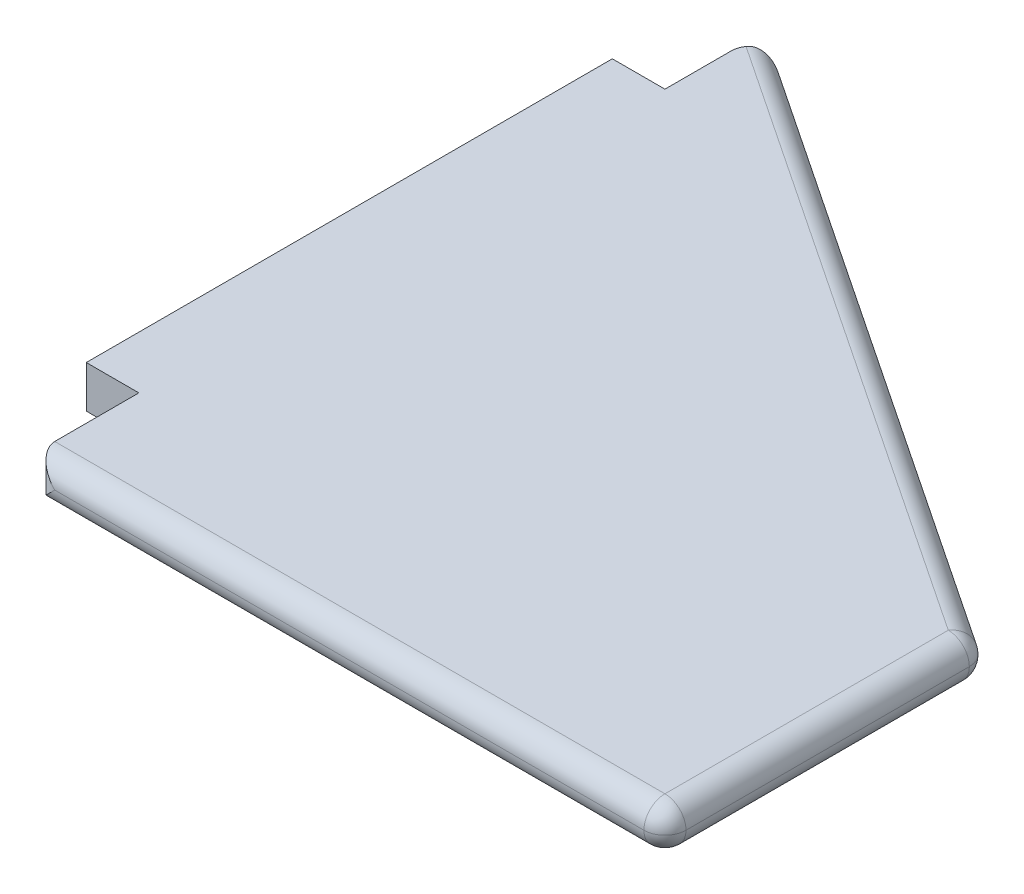
SolidWorks part; units mm, degrees
ref_plane "Front Plane" through (0, 0, 0) normal (0, 0, 1) x (1, 0, 0)
ref_plane "Top Plane" through (0, 0, 0) normal (0, 1, 0) x (1, 0, 0)
ref_plane "Right Plane" through (0, 0, 0) normal (1, 0, 0) x (0, 0, -1)
sketch "Sketch1" plane through (0, 0, 0) normal (0, 1, 0) x (1, 0, 0)
  line L0 (0, 0) -> (0, 31.75)
  line L1 (0, 31.75) -> (3.175, 31.75)
  line L2 (3.175, 31.75) -> (3.175, 38.1)
  line L3 (3.175, 38.1) -> (41.275, 12.7)
  line L4 (41.275, 12.7) -> (41.275, -6.35)
  line L6 (3.175, -6.35) -> (3.175, 0)
  line L7 (3.175, 0) -> (0, 0)
  line L8 (3.175, -6.35) -> (41.275, -6.35)
  point P9 (0, 0)
  point P10 (0, 0)
  dimension "D1" = 38.1
  dimension "D2" = 44.45
  dimension "D3" = 31.75
  dimension "D4" = 19.05
  dimension "D5" = 3.175
extrude "Boss-Extrude1" add sketch "Sketch1" along normal blind 2.54
fillet "Fillet1" radius 1.27 8 edges at (22.225, 2.54, -25.4) (3.175, 1.27, -38.1) (22.225, 0, -25.4) (41.275, 2.54, -3.175) (41.275, 0, -3.175) (3.175, 1.27, 6.35) (22.225, 2.54, 6.35) (22.225, 0, 6.35)
